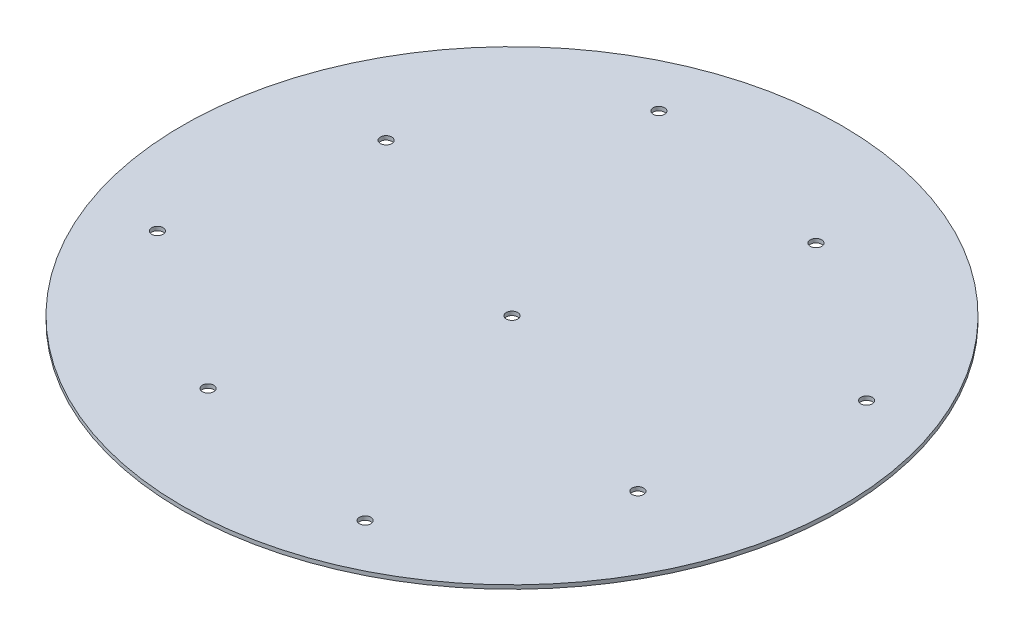
SolidWorks part; units mm, degrees
ref_plane "Front Plane" through (0, 0, 0) normal (0, 0, 1) x (1, 0, 0)
ref_plane "Top Plane" through (0, 0, 0) normal (0, 1, 0) x (1, 0, 0)
ref_plane "Right Plane" through (0, 0, 0) normal (1, 0, 0) x (0, 0, -1)
sketch "Sketch2" plane through (0, 0, 0) normal (1, 0, 0) x (0, 0, -1)
  line L0 (0, 0) -> (-84.9998, 0)
  line L1 (-84.9998, 0) -> (-84.9998, 1)
  line L2 (-84.9998, 1) -> (0, 1)
  line L5 (0, 1) -> (0, 0)
  dimension "D1" = 84.9998
  dimension "D2" = 1
ref_axis "Axis1" through (0, -0.75, 0) along (0, 1, 0)
revolve "Revolve1" add sketch "Sketch2" angle 360 about axis through (0, -0.75, 0) along (0, 1, 0)
hole_wizard "#32 (0.116) Diameter Hole1" positions "Sketch6" profile "Sketch7" hole size "#32" standard "ANSI Inch" end condition through all
sketch "Sketch6" plane through (0, 1, 0) normal (0, 1, 0) x (1, 0, 0)
  line L0 (0, 0) -> (-53.438, 129.0108) construction
  line L2 (0, 0) -> (0, 109.0908) construction
  line L3 (0, 0) -> (-78.5296, 32.528) construction
  circle A0 centre (0, 0) radius 84.9998 construction
  point P0 (-26.7878, 64.6716)
  point P11 (264.7437, 73.7878)
  point P20 (-55.4328, 22.961)
  dimension "D1" = 22.5
  dimension "D2" = 70
  dimension "D3" = 60
  dimension "D4" = 45
sketch "Sketch7" plane through (-26.7878, 1, -64.6716) normal (1, 0, 0) x (0, 0, 1)
  line L0 (0, 0) -> (0, 1)
  line L1 (0, 1) -> (1.4732, 1)
  line L2 (1.4732, 1) -> (1.4732, 0)
  line L5 (1.4732, 0) -> (0, 0)
  line L11 (0, -6.35) -> (0, 107.95) construction
  dimension "Thru Hole Dia." = 2.9464
  dimension "Thru Hole Depth" = 1
pattern_circular "CirPattern3" count 4 over 360 about axis through (0, -0.75, 0) along (0, 1, 0) of "#32 (0.116) Diameter Hole1"
hole_wizard "#32 (0.116) Diameter Hole2" positions "Sketch8" profile "Sketch9" hole size "#32" standard "ANSI Inch" end condition through all
sketch "Sketch8" plane through (0, 1, 0) normal (0, 1, 0) x (1, 0, 0)
  line L0 (0, 0) -> (106.3094, -1.7118) construction
  point P7 (0, 0)
sketch "Sketch9" plane through (0, 1, 0) normal (1, 0, 0) x (0, 0, 1)
  line L0 (0, 0) -> (0, 1)
  line L1 (0, 1) -> (1.4732, 1)
  line L2 (1.4732, 1) -> (1.4732, 0)
  line L5 (1.4732, 0) -> (0, 0)
  line L11 (0, -6.35) -> (0, 107.95) construction
  dimension "Thru Hole Dia." = 2.9464
  dimension "Thru Hole Depth" = 1
